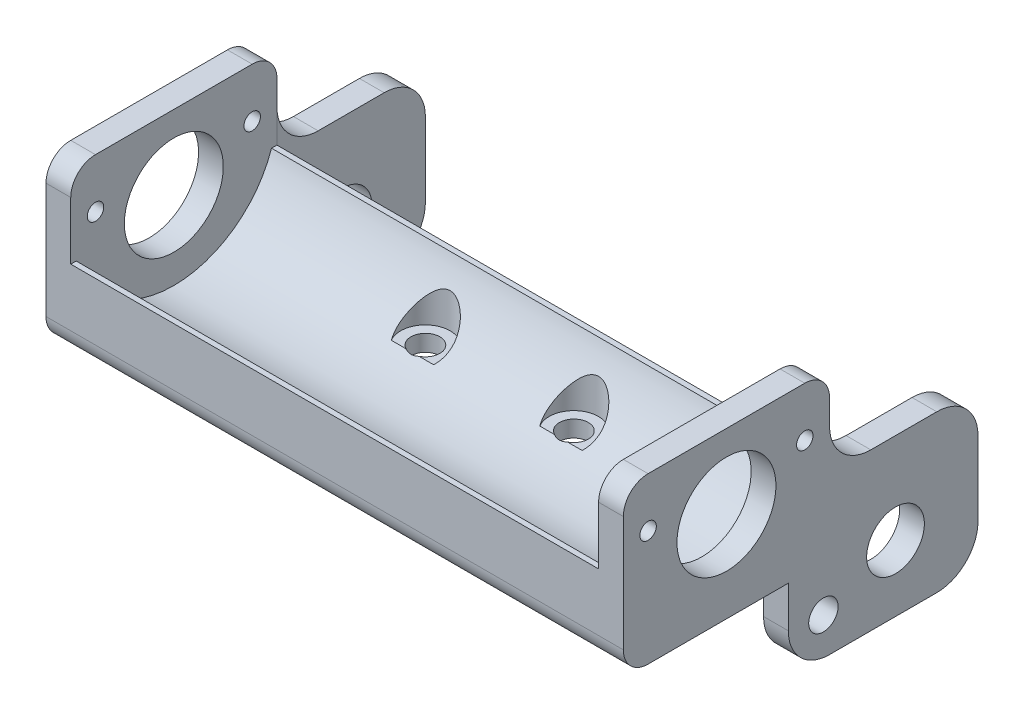
SolidWorks part; units mm, degrees
ref_plane "Front Plane" through (0, 0, 0) normal (0, 0, 1) x (1, 0, 0)
ref_plane "Top Plane" through (0, 0, 0) normal (0, 1, 0) x (1, 0, 0)
ref_plane "Right Plane" through (0, 0, 0) normal (1, 0, 0) x (0, 0, -1)
sketch "Sketch1" plane through (0, 0, 0) normal (0, 1, 0) x (1, 0, 0)
  line L1 (-35, 12.5) -> (35, 12.5)
  line L2 (-35, 12.5) -> (-35, -12.5)
  line L3 (-35, -12.5) -> (35, -12.5)
  line L4 (35, 12.5) -> (35, -12.5)
  line L5 (-35, 12.5) -> (35, -12.5) construction
  line L6 (-35, -12.5) -> (35, 12.5) construction
  point P0 (0, 0)
  dimension "D1" = 70
  dimension "D2" = 25
extrude "Boss-Extrude1" add sketch "Sketch1" along normal blind 10
sketch "Sketch2" plane through (0, 10, 0) normal (0, 1, 0) x (1, 0, 0)
  line L0 (-35, -12.5) -> (35, -12.5) construction
  line L1 (-35, 12.5) -> (-32, 12.5)
  line L2 (-35, 12.5) -> (-35, -12.5)
  line L3 (-35, -12.5) -> (-32, -12.5)
  line L4 (-32, 12.5) -> (-32, -12.5)
  dimension "D1" = 3
extrude "Boss-Extrude2" add sketch "Sketch2" along normal blind 10
sketch "Sketch3" plane through (35, 0, 0) normal (1, 0, 0) x (0, 0, -1)
  line L0 (-12.5, 0) -> (12.5, 0) construction
  circle A0 centre (0, 14) radius 12.5
  dimension "D1" = 25
  dimension "D2" = 14
extrude "Cut-Extrude1" cut sketch "Sketch3" against normal blind 67
ref_plane "Plane1" through (0, 3, 0) normal (0, 1, 0) x (1, 0, 0)
sketch "Sketch4" plane through (0, 3, 0) normal (0, 1, 0) x (1, 0, 0)
  line L0 (-9, 7.5) -> (9, 7.5) construction
  circle A0 centre (-9, 7.5) radius 3
  circle A1 centre (9, 7.5) radius 3
  dimension "D4" = 6
  dimension "D5" = 6
  dimension "D1" = 9
  dimension "D2" = 9
  dimension "D3" = 7.5
extrude "Cut-Extrude2" cut sketch "Sketch4" along normal through all
sketch "Sketch5" plane through (0, 3, 0) normal (0, 1, 0) x (1, 0, 0)
  circle A0 centre (-9, 7.5) radius 1.75
  circle A1 centre (9, 7.5) radius 1.75
  dimension "D1" = 3.5
  dimension "D2" = 3.5
extrude "Cut-Extrude3" cut sketch "Sketch5" against normal through all
sketch "Sketch6" plane through (0, 0, 0) normal (0, -1, 0) x (1, 0, 0)
  line L0 (35, -12.5) -> (-35, -12.5) construction
  line L1 (-14.5, -12.5) -> (14.5, -12.5)
  line L2 (-14.5, -12.5) -> (-14.5, 0.5)
  line L3 (-14.5, 0.5) -> (14.5, 0.5)
  line L4 (14.5, -12.5) -> (14.5, 0.5)
  line L5 (0, 0) -> (0, 0.5) construction
  dimension "D1" = 29
  dimension "D2" = 13
extrude "Cut-Extrude4" cut sketch "Sketch6" against normal blind 1
mirror "Mirror1" about plane through (0, 0, 0) normal (0, 0, 1) of "Cut-Extrude4", "Cut-Extrude3", "Cut-Extrude2"
sketch "Sketch9" plane through (35, 0, 0) normal (1, 0, 0) x (0, 0, -1)
  line L1 (-12.5, 0) -> (12.5, 0)
  line L2 (-12.5, 0) -> (-12.5, 20)
  line L3 (-12.5, 20) -> (12.5, 20)
  line L4 (12.5, 0) -> (12.5, 20)
extrude "Boss-Extrude3" add sketch "Sketch9" against normal blind 3
sketch "Sketch8" plane through (-35, 0, 0) normal (-1, 0, 0) x (0, 0, 1)
  line L0 (0, 11) -> (0, 0) construction
  line L1 (9.5, 14) -> (-9.5, 14) construction
  circle A0 centre (0, 11) radius 6
  circle A1 centre (-9.5, 14) radius 1
  circle A2 centre (9.5, 14) radius 1
  dimension "D2" = 12
  dimension "D6" = 2
  dimension "D7" = 2
  dimension "D1" = 11
  dimension "D3" = 3
  dimension "D4" = 9.5
  dimension "D5" = 9.5
extrude "Cut-Extrude6" cut sketch "Sketch8" against normal through all
fillet "Fillet1" radius 3 4 edges at (33.5, 20, -12.5) (33.5, 20, 12.5) (-33.5, 20, -12.5) (-33.5, 20, 12.5)
sketch "Sketch10" plane through (35, 0, 0) normal (1, 0, 0) x (0, 0, -1)
  line L0 (12.5, 17) -> (12.5, 0) construction
  line L1 (7.5, 9) -> (30.5, 9)
  line L2 (7.5, 9) -> (7.5, -10)
  line L3 (7.5, -10) -> (30.5, -10)
  line L4 (30.5, 9) -> (30.5, -10)
  line L5 (-12.5, 0) -> (12.5, 0) construction
  dimension "D1" = 5
  dimension "D2" = 9
  dimension "D3" = 19
  dimension "D4" = 23
extrude "Boss-Extrude4" add sketch "Sketch10" against normal blind 3
fillet "Fillet2" radius 5 3 edges at (33.5, -10, -30.5) (33.5, 9, -30.5) (33.5, -10, -7.5)
sketch "Sketch11" plane through (35, 0, 0) normal (1, 0, 0) x (0, 0, -1)
  line L0 (30.5, -5) -> (30.5, 4) construction
  line L1 (25.5, 9) -> (12.5, 9) construction
  circle A0 centre (20.5, -2) radius 3.5
  dimension "D3" = 7
  dimension "D1" = 10
  dimension "D2" = 11
extrude "Cut-Extrude7" cut sketch "Sketch11" against normal through all
mirror "Mirror2" about plane through (0, 0, 0) normal (1, 0, 0) of "Cut-Extrude7", "Fillet2", "Boss-Extrude4"
fillet "Fillet3" radius 5 2 edges at (-33.5, 9, -12.5) (33.5, 9, -12.5)
fillet "Fillet4" radius 3 2 edges at (24.75, 0, 12.5) (-23.25, 0, -12.5)
sketch "Sketch12" plane through (-35, 0, 0) normal (-1, 0, 0) x (0, 0, 1)
  circle A0 centre (-11.7553, -5.4608) radius 1.7844
  point P2 (-11.7553, -5.4608)
extrude "Cut-Extrude8" cut sketch "Sketch12" against normal through all
